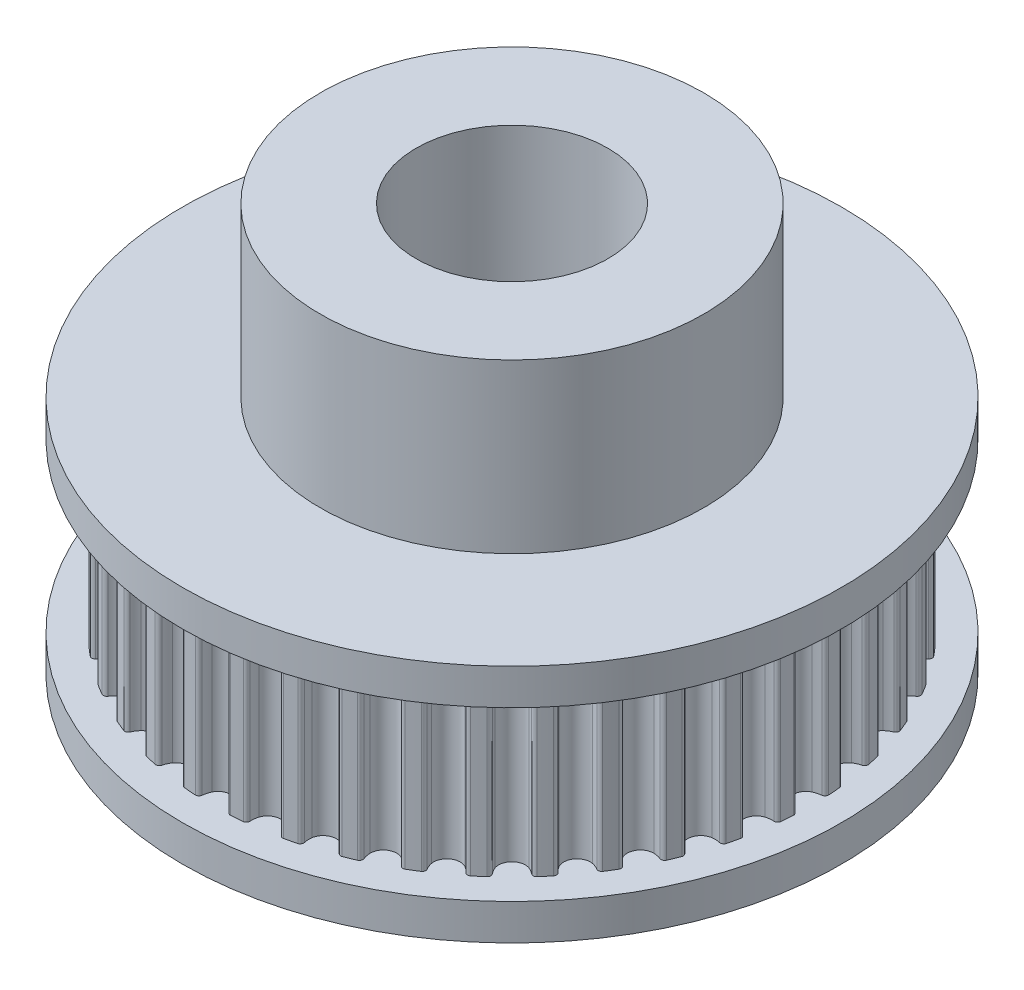
SolidWorks part; units mm, degrees
ref_plane "Front" through (0, 0, 0) normal (0, 0, 1) x (1, 0, 0)
ref_plane "Top" through (0, 0, 0) normal (0, 1, 0) x (1, 0, 0)
ref_plane "Right" through (0, 0, 0) normal (1, 0, 0) x (0, 0, -1)
sketch "Sketch1" plane through (0, 0, 0) normal (0, 0, 1) x (1, 0, 0)
  line L0 (0, 0) -> (0, 8.3172) construction
  line L1 (0, 0) -> (4, 0) construction
  line L2 (4, 0) -> (4, 17)
  line L3 (4, 0) -> (13.75, 0)
  line L4 (13.75, 0) -> (13.75, 1.5)
  line L5 (13.75, 1.5) -> (9.193, 1.5)
  line L6 (9.193, 1.5) -> (9.193, 8.5)
  line L7 (9.193, 8.5) -> (13.75, 8.5)
  line L8 (13.75, 8.5) -> (13.75, 10)
  line L9 (13.75, 10) -> (8, 10)
  line L10 (8, 10) -> (8, 17)
  line L11 (8, 17) -> (4, 17)
  dimension "D1" = 27.5
  dimension "D2" = 8
  dimension "D3" = 17
  dimension "D4" = 7
  dimension "D5" = 16
  dimension "D6" = 10
revolve "Revolve1" add sketch "Sketch1" angle 360 about L0
sketch "Sketch2" plane through (0, 1.5, 0) normal (0, 1, 0) x (1, 0, 0)
  circle A0 centre (0, 0) radius 4
  arc A1 (12.4796, -0.7303) -> (12.349, -0.5816) centre (12.3296, -0.7303) ccw
  arc A2 (12.0252, -0.4964) -> (12.349, -0.5816) centre (12.4379, 0.4144) ccw
  arc A3 (11.7184, 0) -> (12.0252, -0.4964) centre (12.2734, 0) ccw
  arc A4 (12.0252, 0.4964) -> (11.7184, 0) centre (12.2734, 0) ccw
  arc A5 (12.349, 0.5816) -> (12.0252, 0.4964) centre (12.4379, -0.4144) ccw
  arc A6 (12.349, 0.5816) -> (12.4796, 0.7303) centre (12.3296, 0.7303) ccw
  arc A7 (12.4796, 0.7303) -> (12.4402, 1.2309) centre (0.0225, 0.0018) ccw
  arc A8 (12.4402, 1.2309) -> (12.288, 1.3574) centre (12.2921, 1.2074) ccw
  arc A9 (11.9548, 1.3909) -> (12.288, 1.3574) centre (12.2199, 2.3551) ccw
  arc A10 (11.5741, 1.8332) -> (11.9548, 1.3909) centre (12.1223, 1.92) ccw
  arc A11 (11.7995, 2.3714) -> (11.5741, 1.8332) centre (12.1223, 1.92) ccw
  arc A12 (12.106, 2.5063) -> (11.7995, 2.3714) centre (12.3496, 1.5364) ccw
  arc A13 (12.106, 2.5063) -> (12.2117, 2.6736) centre (12.0636, 2.6501) ccw
  arc A14 (12.2117, 2.6736) -> (12.0945, 3.1618) centre (0.022, 0.0053) ccw
  arc A15 (12.0945, 3.1618) -> (11.9244, 3.2629) centre (11.9519, 3.1155) ccw
  arc A16 (11.59, 3.2439) -> (11.9244, 3.2629) centre (11.7011, 4.2377) ccw
  arc A17 (11.1448, 3.6212) -> (11.59, 3.2439) centre (11.6727, 3.7927) ccw
  arc A18 (11.2832, 4.1881) -> (11.1448, 3.6212) centre (11.6727, 3.7927) ccw
  arc A19 (11.5649, 4.3692) -> (11.2832, 4.1881) centre (11.9572, 3.4494) ccw
  arc A20 (11.5649, 4.3692) -> (11.6431, 4.551) centre (11.5005, 4.5047) ccw
  arc A21 (11.6431, 4.551) -> (11.451, 5.0149) centre (0.0209, 0.0087) ccw
  arc A22 (11.451, 5.0149) -> (11.2671, 5.0881) centre (11.3173, 4.9468) ccw
  arc A23 (10.9399, 5.017) -> (11.2671, 5.0881) centre (10.8941, 6.016) ccw
  arc A24 (10.4411, 5.32) -> (10.9399, 5.017) centre (10.9357, 5.572) ccw
  arc A25 (10.4891, 5.9016) -> (10.4411, 5.32) centre (10.9357, 5.572) ccw
  arc A26 (10.739, 6.1246) -> (10.4891, 5.9016) centre (11.2704, 5.2774) ccw
  arc A27 (10.739, 6.1246) -> (10.7879, 6.3164) centre (10.6542, 6.2483) ccw
  arc A28 (10.7879, 6.3164) -> (10.5255, 6.7445) centre (0.0193, 0.0118) ccw
  arc A29 (10.5255, 6.7445) -> (10.3324, 6.7881) centre (10.4042, 6.6563) ccw
  arc A30 (10.0203, 6.6666) -> (10.3324, 6.7881) centre (9.8189, 7.6461) ccw
  arc A31 (9.4804, 6.8879) -> (10.0203, 6.6666) centre (9.9294, 7.2141) ccw
  arc A32 (9.4368, 7.4698) -> (9.4804, 6.8879) centre (9.9294, 7.2141) ccw
  arc A33 (9.6487, 7.7291) -> (9.4368, 7.4698) centre (10.3061, 6.9755) ccw
  arc A34 (9.6487, 7.7291) -> (9.667, 7.9262) centre (9.5456, 7.838) ccw
  arc A35 (9.667, 7.9262) -> (9.3409, 8.308) centre (0.0172, 0.0147) ccw
  arc A36 (9.3409, 8.308) -> (9.1433, 8.3208) centre (9.2348, 8.2019) ccw
  arc A37 (8.8541, 8.1521) -> (9.1433, 8.3208) centre (8.5019, 9.088) ccw
  arc A38 (8.2861, 8.2861) -> (8.8541, 8.1521) centre (8.6786, 8.6786) ccw
  arc A39 (8.1521, 8.8541) -> (8.2861, 8.2861) centre (8.6786, 8.6786) ccw
  arc A40 (8.3208, 9.1433) -> (8.1521, 8.8541) centre (9.088, 8.5019) ccw
  arc A41 (8.3208, 9.1433) -> (8.308, 9.3409) centre (8.2019, 9.2348) ccw
  arc A42 (8.308, 9.3409) -> (7.9262, 9.667) centre (0.0147, 0.0172) ccw
  arc A43 (7.9262, 9.667) -> (7.7291, 9.6487) centre (7.838, 9.5456) ccw
  arc A44 (7.4698, 9.4368) -> (7.7291, 9.6487) centre (6.9755, 10.3061) ccw
  arc A45 (6.8879, 9.4804) -> (7.4698, 9.4368) centre (7.2141, 9.9294) ccw
  arc A46 (6.6666, 10.0203) -> (6.8879, 9.4804) centre (7.2141, 9.9294) ccw
  arc A47 (6.7881, 10.3324) -> (6.6666, 10.0203) centre (7.6461, 9.8189) ccw
  arc A48 (6.7881, 10.3324) -> (6.7445, 10.5255) centre (6.6563, 10.4042) ccw
  arc A49 (6.7445, 10.5255) -> (6.3164, 10.7879) centre (0.0118, 0.0193) ccw
  arc A50 (6.3164, 10.7879) -> (6.1246, 10.739) centre (6.2483, 10.6542) ccw
  arc A51 (5.9016, 10.4891) -> (6.1246, 10.739) centre (5.2774, 11.2704) ccw
  arc A52 (5.32, 10.4411) -> (5.9016, 10.4891) centre (5.572, 10.9357) ccw
  arc A53 (5.017, 10.9399) -> (5.32, 10.4411) centre (5.572, 10.9357) ccw
  arc A54 (5.0881, 11.2671) -> (5.017, 10.9399) centre (6.016, 10.8941) ccw
  arc A55 (5.0881, 11.2671) -> (5.0149, 11.451) centre (4.9468, 11.3173) ccw
  arc A56 (5.0149, 11.451) -> (4.551, 11.6431) centre (0.0087, 0.0209) ccw
  arc A57 (4.551, 11.6431) -> (4.3692, 11.5649) centre (4.5047, 11.5005) ccw
  arc A58 (4.1881, 11.2832) -> (4.3692, 11.5649) centre (3.4494, 11.9572) ccw
  arc A59 (3.6212, 11.1448) -> (4.1881, 11.2832) centre (3.7927, 11.6727) ccw
  arc A60 (3.2439, 11.59) -> (3.6212, 11.1448) centre (3.7927, 11.6727) ccw
  arc A61 (3.2629, 11.9244) -> (3.2439, 11.59) centre (4.2377, 11.7011) ccw
  arc A62 (3.2629, 11.9244) -> (3.1618, 12.0945) centre (3.1155, 11.9519) ccw
  arc A63 (3.1618, 12.0945) -> (2.6736, 12.2117) centre (0.0053, 0.022) ccw
  arc A64 (2.6736, 12.2117) -> (2.5063, 12.106) centre (2.6501, 12.0636) ccw
  arc A65 (2.3714, 11.7995) -> (2.5063, 12.106) centre (1.5364, 12.3496) ccw
  arc A66 (1.8332, 11.5741) -> (2.3714, 11.7995) centre (1.92, 12.1223) ccw
  arc A67 (1.3909, 11.9548) -> (1.8332, 11.5741) centre (1.92, 12.1223) ccw
  arc A68 (1.3574, 12.288) -> (1.3909, 11.9548) centre (2.3551, 12.2199) ccw
  arc A69 (1.3574, 12.288) -> (1.2309, 12.4402) centre (1.2074, 12.2921) ccw
  arc A70 (1.2309, 12.4402) -> (0.7303, 12.4796) centre (0.0018, 0.0225) ccw
  arc A71 (0.7303, 12.4796) -> (0.5816, 12.349) centre (0.7303, 12.3296) ccw
  arc A72 (0.4964, 12.0252) -> (0.5816, 12.349) centre (-0.4144, 12.4379) ccw
  arc A73 (0, 11.7184) -> (0.4964, 12.0252) centre (0, 12.2734) ccw
  arc A74 (-0.4964, 12.0252) -> (0, 11.7184) centre (0, 12.2734) ccw
  arc A75 (-0.5816, 12.349) -> (-0.4964, 12.0252) centre (0.4144, 12.4379) ccw
  arc A76 (-0.5816, 12.349) -> (-0.7303, 12.4796) centre (-0.7303, 12.3296) ccw
  arc A77 (-0.7303, 12.4796) -> (-1.2309, 12.4402) centre (-0.0018, 0.0225) ccw
  arc A78 (-1.2309, 12.4402) -> (-1.3574, 12.288) centre (-1.2074, 12.2921) ccw
  arc A79 (-1.3909, 11.9548) -> (-1.3574, 12.288) centre (-2.3551, 12.2199) ccw
  arc A80 (-1.8332, 11.5741) -> (-1.3909, 11.9548) centre (-1.92, 12.1223) ccw
  arc A81 (-2.3714, 11.7995) -> (-1.8332, 11.5741) centre (-1.92, 12.1223) ccw
  arc A82 (-2.5063, 12.106) -> (-2.3714, 11.7995) centre (-1.5364, 12.3496) ccw
  arc A83 (-2.5063, 12.106) -> (-2.6736, 12.2117) centre (-2.6501, 12.0636) ccw
  arc A84 (-2.6736, 12.2117) -> (-3.1618, 12.0945) centre (-0.0053, 0.022) ccw
  arc A85 (-3.1618, 12.0945) -> (-3.2629, 11.9244) centre (-3.1155, 11.9519) ccw
  arc A86 (-3.2439, 11.59) -> (-3.2629, 11.9244) centre (-4.2377, 11.7011) ccw
  arc A87 (-3.6212, 11.1448) -> (-3.2439, 11.59) centre (-3.7927, 11.6727) ccw
  arc A88 (-4.1881, 11.2832) -> (-3.6212, 11.1448) centre (-3.7927, 11.6727) ccw
  arc A89 (-4.3692, 11.5649) -> (-4.1881, 11.2832) centre (-3.4494, 11.9572) ccw
  arc A90 (-4.3692, 11.5649) -> (-4.551, 11.6431) centre (-4.5047, 11.5005) ccw
  arc A91 (-4.551, 11.6431) -> (-5.0149, 11.451) centre (-0.0087, 0.0209) ccw
  arc A92 (-5.0149, 11.451) -> (-5.0881, 11.2671) centre (-4.9468, 11.3173) ccw
  arc A93 (-5.017, 10.9399) -> (-5.0881, 11.2671) centre (-6.016, 10.8941) ccw
  arc A94 (-5.32, 10.4411) -> (-5.017, 10.9399) centre (-5.572, 10.9357) ccw
  arc A95 (-5.9016, 10.4891) -> (-5.32, 10.4411) centre (-5.572, 10.9357) ccw
  arc A96 (-6.1246, 10.739) -> (-5.9016, 10.4891) centre (-5.2774, 11.2704) ccw
  arc A97 (-6.1246, 10.739) -> (-6.3164, 10.7879) centre (-6.2483, 10.6542) ccw
  arc A98 (-6.3164, 10.7879) -> (-6.7445, 10.5255) centre (-0.0118, 0.0193) ccw
  arc A99 (-6.7445, 10.5255) -> (-6.7881, 10.3324) centre (-6.6563, 10.4042) ccw
  arc A100 (-6.6666, 10.0203) -> (-6.7881, 10.3324) centre (-7.6461, 9.8189) ccw
  arc A101 (-6.8879, 9.4804) -> (-6.6666, 10.0203) centre (-7.2141, 9.9294) ccw
  arc A102 (-7.4698, 9.4368) -> (-6.8879, 9.4804) centre (-7.2141, 9.9294) ccw
  arc A103 (-7.7291, 9.6487) -> (-7.4698, 9.4368) centre (-6.9755, 10.3061) ccw
  arc A104 (-7.7291, 9.6487) -> (-7.9262, 9.667) centre (-7.838, 9.5456) ccw
  arc A105 (-7.9262, 9.667) -> (-8.308, 9.3409) centre (-0.0147, 0.0172) ccw
  arc A106 (-8.308, 9.3409) -> (-8.3208, 9.1433) centre (-8.2019, 9.2348) ccw
  arc A107 (-8.1521, 8.8541) -> (-8.3208, 9.1433) centre (-9.088, 8.5019) ccw
  arc A108 (-8.2861, 8.2861) -> (-8.1521, 8.8541) centre (-8.6786, 8.6786) ccw
  arc A109 (-8.8541, 8.1521) -> (-8.2861, 8.2861) centre (-8.6786, 8.6786) ccw
  arc A110 (-9.1433, 8.3208) -> (-8.8541, 8.1521) centre (-8.5019, 9.088) ccw
  arc A111 (-9.1433, 8.3208) -> (-9.3409, 8.308) centre (-9.2348, 8.2019) ccw
  arc A112 (-9.3409, 8.308) -> (-9.667, 7.9262) centre (-0.0172, 0.0147) ccw
  arc A113 (-9.667, 7.9262) -> (-9.6487, 7.7291) centre (-9.5456, 7.838) ccw
  arc A114 (-9.4368, 7.4698) -> (-9.6487, 7.7291) centre (-10.3061, 6.9755) ccw
  arc A115 (-9.4804, 6.8879) -> (-9.4368, 7.4698) centre (-9.9294, 7.2141) ccw
  arc A116 (-10.0203, 6.6666) -> (-9.4804, 6.8879) centre (-9.9294, 7.2141) ccw
  arc A117 (-10.3324, 6.7881) -> (-10.0203, 6.6666) centre (-9.8189, 7.6461) ccw
  arc A118 (-10.3324, 6.7881) -> (-10.5255, 6.7445) centre (-10.4042, 6.6563) ccw
  arc A119 (-10.5255, 6.7445) -> (-10.7879, 6.3164) centre (-0.0193, 0.0118) ccw
  arc A120 (-10.7879, 6.3164) -> (-10.739, 6.1246) centre (-10.6542, 6.2483) ccw
  arc A121 (-10.4891, 5.9016) -> (-10.739, 6.1246) centre (-11.2704, 5.2774) ccw
  arc A122 (-10.4411, 5.32) -> (-10.4891, 5.9016) centre (-10.9357, 5.572) ccw
  arc A123 (-10.9399, 5.017) -> (-10.4411, 5.32) centre (-10.9357, 5.572) ccw
  arc A124 (-11.2671, 5.0881) -> (-10.9399, 5.017) centre (-10.8941, 6.016) ccw
  arc A125 (-11.2671, 5.0881) -> (-11.451, 5.0149) centre (-11.3173, 4.9468) ccw
  arc A126 (-11.451, 5.0149) -> (-11.6431, 4.551) centre (-0.0209, 0.0087) ccw
  arc A127 (-11.6431, 4.551) -> (-11.5649, 4.3692) centre (-11.5005, 4.5047) ccw
  arc A128 (-11.2832, 4.1881) -> (-11.5649, 4.3692) centre (-11.9572, 3.4494) ccw
  arc A129 (-11.1448, 3.6212) -> (-11.2832, 4.1881) centre (-11.6727, 3.7927) ccw
  arc A130 (-11.59, 3.2439) -> (-11.1448, 3.6212) centre (-11.6727, 3.7927) ccw
  arc A131 (-11.9244, 3.2629) -> (-11.59, 3.2439) centre (-11.7011, 4.2377) ccw
  arc A132 (-11.9244, 3.2629) -> (-12.0945, 3.1618) centre (-11.9519, 3.1155) ccw
  arc A133 (-12.0945, 3.1618) -> (-12.2117, 2.6736) centre (-0.022, 0.0053) ccw
  arc A134 (-12.2117, 2.6736) -> (-12.106, 2.5063) centre (-12.0636, 2.6501) ccw
  arc A135 (-11.7995, 2.3714) -> (-12.106, 2.5063) centre (-12.3496, 1.5364) ccw
  arc A136 (-11.5741, 1.8332) -> (-11.7995, 2.3714) centre (-12.1223, 1.92) ccw
  arc A137 (-11.9548, 1.3909) -> (-11.5741, 1.8332) centre (-12.1223, 1.92) ccw
  arc A138 (-12.288, 1.3574) -> (-11.9548, 1.3909) centre (-12.2199, 2.3551) ccw
  arc A139 (-12.288, 1.3574) -> (-12.4402, 1.2309) centre (-12.2921, 1.2074) ccw
  arc A140 (-12.4402, 1.2309) -> (-12.4796, 0.7303) centre (-0.0225, 0.0018) ccw
  arc A141 (-12.4796, 0.7303) -> (-12.349, 0.5816) centre (-12.3296, 0.7303) ccw
  arc A142 (-12.0252, 0.4964) -> (-12.349, 0.5816) centre (-12.4379, -0.4144) ccw
  arc A143 (-11.7184, 0) -> (-12.0252, 0.4964) centre (-12.2734, 0) ccw
  arc A144 (-12.0252, -0.4964) -> (-11.7184, 0) centre (-12.2734, 0) ccw
  arc A145 (-12.349, -0.5816) -> (-12.0252, -0.4964) centre (-12.4379, 0.4144) ccw
  arc A146 (-12.349, -0.5816) -> (-12.4796, -0.7303) centre (-12.3296, -0.7303) ccw
  arc A147 (-12.4796, -0.7303) -> (-12.4402, -1.2309) centre (-0.0225, -0.0018) ccw
  arc A148 (-12.4402, -1.2309) -> (-12.288, -1.3574) centre (-12.2921, -1.2074) ccw
  arc A149 (-11.9548, -1.3909) -> (-12.288, -1.3574) centre (-12.2199, -2.3551) ccw
  arc A150 (-11.5741, -1.8332) -> (-11.9548, -1.3909) centre (-12.1223, -1.92) ccw
  arc A151 (-11.7995, -2.3714) -> (-11.5741, -1.8332) centre (-12.1223, -1.92) ccw
  arc A152 (-12.106, -2.5063) -> (-11.7995, -2.3714) centre (-12.3496, -1.5364) ccw
  arc A153 (-12.106, -2.5063) -> (-12.2117, -2.6736) centre (-12.0636, -2.6501) ccw
  arc A154 (-12.2117, -2.6736) -> (-12.0945, -3.1618) centre (-0.022, -0.0053) ccw
  arc A155 (-12.0945, -3.1618) -> (-11.9244, -3.2629) centre (-11.9519, -3.1155) ccw
  arc A156 (-11.59, -3.2439) -> (-11.9244, -3.2629) centre (-11.7011, -4.2377) ccw
  arc A157 (-11.1448, -3.6212) -> (-11.59, -3.2439) centre (-11.6727, -3.7927) ccw
  arc A158 (-11.2832, -4.1881) -> (-11.1448, -3.6212) centre (-11.6727, -3.7927) ccw
  arc A159 (-11.5649, -4.3692) -> (-11.2832, -4.1881) centre (-11.9572, -3.4494) ccw
  arc A160 (-11.5649, -4.3692) -> (-11.6431, -4.551) centre (-11.5005, -4.5047) ccw
  arc A161 (-11.6431, -4.551) -> (-11.451, -5.0149) centre (-0.0209, -0.0087) ccw
  arc A162 (-11.451, -5.0149) -> (-11.2671, -5.0881) centre (-11.3173, -4.9468) ccw
  arc A163 (-10.9399, -5.017) -> (-11.2671, -5.0881) centre (-10.8941, -6.016) ccw
  arc A164 (-10.4411, -5.32) -> (-10.9399, -5.017) centre (-10.9357, -5.572) ccw
  arc A165 (-10.4891, -5.9016) -> (-10.4411, -5.32) centre (-10.9357, -5.572) ccw
  arc A166 (-10.739, -6.1246) -> (-10.4891, -5.9016) centre (-11.2704, -5.2774) ccw
  arc A167 (-10.739, -6.1246) -> (-10.7879, -6.3164) centre (-10.6542, -6.2483) ccw
  arc A168 (-10.7879, -6.3164) -> (-10.5255, -6.7445) centre (-0.0193, -0.0118) ccw
  arc A169 (-10.5255, -6.7445) -> (-10.3324, -6.7881) centre (-10.4042, -6.6563) ccw
  arc A170 (-10.0203, -6.6666) -> (-10.3324, -6.7881) centre (-9.8189, -7.6461) ccw
  arc A171 (-9.4804, -6.8879) -> (-10.0203, -6.6666) centre (-9.9294, -7.2141) ccw
  arc A172 (-9.4368, -7.4698) -> (-9.4804, -6.8879) centre (-9.9294, -7.2141) ccw
  arc A173 (-9.6487, -7.7291) -> (-9.4368, -7.4698) centre (-10.3061, -6.9755) ccw
  arc A174 (-9.6487, -7.7291) -> (-9.667, -7.9262) centre (-9.5456, -7.838) ccw
  arc A175 (-9.667, -7.9262) -> (-9.3409, -8.308) centre (-0.0172, -0.0147) ccw
  arc A176 (-9.3409, -8.308) -> (-9.1433, -8.3208) centre (-9.2348, -8.2019) ccw
  arc A177 (-8.8541, -8.1521) -> (-9.1433, -8.3208) centre (-8.5019, -9.088) ccw
  arc A178 (-8.2861, -8.2861) -> (-8.8541, -8.1521) centre (-8.6786, -8.6786) ccw
  arc A179 (-8.1521, -8.8541) -> (-8.2861, -8.2861) centre (-8.6786, -8.6786) ccw
  arc A180 (-8.3208, -9.1433) -> (-8.1521, -8.8541) centre (-9.088, -8.5019) ccw
  arc A181 (-8.3208, -9.1433) -> (-8.308, -9.3409) centre (-8.2019, -9.2348) ccw
  arc A182 (-8.308, -9.3409) -> (-7.9262, -9.667) centre (-0.0147, -0.0172) ccw
  arc A183 (-7.9262, -9.667) -> (-7.7291, -9.6487) centre (-7.838, -9.5456) ccw
  arc A184 (-7.4698, -9.4368) -> (-7.7291, -9.6487) centre (-6.9755, -10.3061) ccw
  arc A185 (-6.8879, -9.4804) -> (-7.4698, -9.4368) centre (-7.2141, -9.9294) ccw
  arc A186 (-6.6666, -10.0203) -> (-6.8879, -9.4804) centre (-7.2141, -9.9294) ccw
  arc A187 (-6.7881, -10.3324) -> (-6.6666, -10.0203) centre (-7.6461, -9.8189) ccw
  arc A188 (-6.7881, -10.3324) -> (-6.7445, -10.5255) centre (-6.6563, -10.4042) ccw
  arc A189 (-6.7445, -10.5255) -> (-6.3164, -10.7879) centre (-0.0118, -0.0193) ccw
  arc A190 (-6.3164, -10.7879) -> (-6.1246, -10.739) centre (-6.2483, -10.6542) ccw
  arc A191 (-5.9016, -10.4891) -> (-6.1246, -10.739) centre (-5.2774, -11.2704) ccw
  arc A192 (-5.32, -10.4411) -> (-5.9016, -10.4891) centre (-5.572, -10.9357) ccw
  arc A193 (-5.017, -10.9399) -> (-5.32, -10.4411) centre (-5.572, -10.9357) ccw
  arc A194 (-5.0881, -11.2671) -> (-5.017, -10.9399) centre (-6.016, -10.8941) ccw
  arc A195 (-5.0881, -11.2671) -> (-5.0149, -11.451) centre (-4.9468, -11.3173) ccw
  arc A196 (-5.0149, -11.451) -> (-4.551, -11.6431) centre (-0.0087, -0.0209) ccw
  arc A197 (-4.551, -11.6431) -> (-4.3692, -11.5649) centre (-4.5047, -11.5005) ccw
  arc A198 (-4.1881, -11.2832) -> (-4.3692, -11.5649) centre (-3.4494, -11.9572) ccw
  arc A199 (-3.6212, -11.1448) -> (-4.1881, -11.2832) centre (-3.7927, -11.6727) ccw
  arc A200 (-3.2439, -11.59) -> (-3.6212, -11.1448) centre (-3.7927, -11.6727) ccw
  arc A201 (-3.2629, -11.9244) -> (-3.2439, -11.59) centre (-4.2377, -11.7011) ccw
  arc A202 (-3.2629, -11.9244) -> (-3.1618, -12.0945) centre (-3.1155, -11.9519) ccw
  arc A203 (-3.1618, -12.0945) -> (-2.6736, -12.2117) centre (-0.0053, -0.022) ccw
  arc A204 (-2.6736, -12.2117) -> (-2.5063, -12.106) centre (-2.6501, -12.0636) ccw
  arc A205 (-2.3714, -11.7995) -> (-2.5063, -12.106) centre (-1.5364, -12.3496) ccw
  arc A206 (-1.8332, -11.5741) -> (-2.3714, -11.7995) centre (-1.92, -12.1223) ccw
  arc A207 (-1.3909, -11.9548) -> (-1.8332, -11.5741) centre (-1.92, -12.1223) ccw
  arc A208 (-1.3574, -12.288) -> (-1.3909, -11.9548) centre (-2.3551, -12.2199) ccw
  arc A209 (-1.3574, -12.288) -> (-1.2309, -12.4402) centre (-1.2074, -12.2921) ccw
  arc A210 (-1.2309, -12.4402) -> (-0.7303, -12.4796) centre (-0.0018, -0.0225) ccw
  arc A211 (-0.7303, -12.4796) -> (-0.5816, -12.349) centre (-0.7303, -12.3296) ccw
  arc A212 (-0.4964, -12.0252) -> (-0.5816, -12.349) centre (0.4144, -12.4379) ccw
  arc A213 (0, -11.7184) -> (-0.4964, -12.0252) centre (0, -12.2734) ccw
  arc A214 (0.4964, -12.0252) -> (0, -11.7184) centre (0, -12.2734) ccw
  arc A215 (0.5816, -12.349) -> (0.4964, -12.0252) centre (-0.4144, -12.4379) ccw
  arc A216 (0.5816, -12.349) -> (0.7303, -12.4796) centre (0.7303, -12.3296) ccw
  arc A217 (0.7303, -12.4796) -> (1.2309, -12.4402) centre (0.0018, -0.0225) ccw
  arc A218 (1.2309, -12.4402) -> (1.3574, -12.288) centre (1.2074, -12.2921) ccw
  arc A219 (1.3909, -11.9548) -> (1.3574, -12.288) centre (2.3551, -12.2199) ccw
  arc A220 (1.8332, -11.5741) -> (1.3909, -11.9548) centre (1.92, -12.1223) ccw
  arc A221 (2.3714, -11.7995) -> (1.8332, -11.5741) centre (1.92, -12.1223) ccw
  arc A222 (2.5063, -12.106) -> (2.3714, -11.7995) centre (1.5364, -12.3496) ccw
  arc A223 (2.5063, -12.106) -> (2.6736, -12.2117) centre (2.6501, -12.0636) ccw
  arc A224 (2.6736, -12.2117) -> (3.1618, -12.0945) centre (0.0053, -0.022) ccw
  arc A225 (3.1618, -12.0945) -> (3.2629, -11.9244) centre (3.1155, -11.9519) ccw
  arc A226 (3.2439, -11.59) -> (3.2629, -11.9244) centre (4.2377, -11.7011) ccw
  arc A227 (3.6212, -11.1448) -> (3.2439, -11.59) centre (3.7927, -11.6727) ccw
  arc A228 (4.1881, -11.2832) -> (3.6212, -11.1448) centre (3.7927, -11.6727) ccw
  arc A229 (4.3692, -11.5649) -> (4.1881, -11.2832) centre (3.4494, -11.9572) ccw
  arc A230 (4.3692, -11.5649) -> (4.551, -11.6431) centre (4.5047, -11.5005) ccw
  arc A231 (4.551, -11.6431) -> (5.0149, -11.451) centre (0.0087, -0.0209) ccw
  arc A232 (5.0149, -11.451) -> (5.0881, -11.2671) centre (4.9468, -11.3173) ccw
  arc A233 (5.017, -10.9399) -> (5.0881, -11.2671) centre (6.016, -10.8941) ccw
  arc A234 (5.32, -10.4411) -> (5.017, -10.9399) centre (5.572, -10.9357) ccw
  arc A235 (5.9016, -10.4891) -> (5.32, -10.4411) centre (5.572, -10.9357) ccw
  arc A236 (6.1246, -10.739) -> (5.9016, -10.4891) centre (5.2774, -11.2704) ccw
  arc A237 (6.1246, -10.739) -> (6.3164, -10.7879) centre (6.2483, -10.6542) ccw
  arc A238 (6.3164, -10.7879) -> (6.7445, -10.5255) centre (0.0118, -0.0193) ccw
  arc A239 (6.7445, -10.5255) -> (6.7881, -10.3324) centre (6.6563, -10.4042) ccw
  arc A240 (6.6666, -10.0203) -> (6.7881, -10.3324) centre (7.6461, -9.8189) ccw
  arc A241 (6.8879, -9.4804) -> (6.6666, -10.0203) centre (7.2141, -9.9294) ccw
  arc A242 (7.4698, -9.4368) -> (6.8879, -9.4804) centre (7.2141, -9.9294) ccw
  arc A243 (7.7291, -9.6487) -> (7.4698, -9.4368) centre (6.9755, -10.3061) ccw
  arc A244 (7.7291, -9.6487) -> (7.9262, -9.667) centre (7.838, -9.5456) ccw
  arc A245 (7.9262, -9.667) -> (8.308, -9.3409) centre (0.0147, -0.0172) ccw
  arc A246 (8.308, -9.3409) -> (8.3208, -9.1433) centre (8.2019, -9.2348) ccw
  arc A247 (8.1521, -8.8541) -> (8.3208, -9.1433) centre (9.088, -8.5019) ccw
  arc A248 (8.2861, -8.2861) -> (8.1521, -8.8541) centre (8.6786, -8.6786) ccw
  arc A249 (8.8541, -8.1521) -> (8.2861, -8.2861) centre (8.6786, -8.6786) ccw
  arc A250 (9.1433, -8.3208) -> (8.8541, -8.1521) centre (8.5019, -9.088) ccw
  arc A251 (9.1433, -8.3208) -> (9.3409, -8.308) centre (9.2348, -8.2019) ccw
  arc A252 (9.3409, -8.308) -> (9.667, -7.9262) centre (0.0172, -0.0147) ccw
  arc A253 (9.667, -7.9262) -> (9.6487, -7.7291) centre (9.5456, -7.838) ccw
  arc A254 (9.4368, -7.4698) -> (9.6487, -7.7291) centre (10.3061, -6.9755) ccw
  arc A255 (9.4804, -6.8879) -> (9.4368, -7.4698) centre (9.9294, -7.2141) ccw
  arc A256 (10.0203, -6.6666) -> (9.4804, -6.8879) centre (9.9294, -7.2141) ccw
  arc A257 (10.3324, -6.7881) -> (10.0203, -6.6666) centre (9.8189, -7.6461) ccw
  arc A258 (10.3324, -6.7881) -> (10.5255, -6.7445) centre (10.4042, -6.6563) ccw
  arc A259 (10.5255, -6.7445) -> (10.7879, -6.3164) centre (0.0193, -0.0118) ccw
  arc A260 (10.7879, -6.3164) -> (10.739, -6.1246) centre (10.6542, -6.2483) ccw
  arc A261 (10.4891, -5.9016) -> (10.739, -6.1246) centre (11.2704, -5.2774) ccw
  arc A262 (10.4411, -5.32) -> (10.4891, -5.9016) centre (10.9357, -5.572) ccw
  arc A263 (10.9399, -5.017) -> (10.4411, -5.32) centre (10.9357, -5.572) ccw
  arc A264 (11.2671, -5.0881) -> (10.9399, -5.017) centre (10.8941, -6.016) ccw
  arc A265 (11.2671, -5.0881) -> (11.451, -5.0149) centre (11.3173, -4.9468) ccw
  arc A266 (11.451, -5.0149) -> (11.6431, -4.551) centre (0.0209, -0.0087) ccw
  arc A267 (11.6431, -4.551) -> (11.5649, -4.3692) centre (11.5005, -4.5047) ccw
  arc A268 (11.2832, -4.1881) -> (11.5649, -4.3692) centre (11.9572, -3.4494) ccw
  arc A269 (11.1448, -3.6212) -> (11.2832, -4.1881) centre (11.6727, -3.7927) ccw
  arc A270 (11.59, -3.2439) -> (11.1448, -3.6212) centre (11.6727, -3.7927) ccw
  arc A271 (11.9244, -3.2629) -> (11.59, -3.2439) centre (11.7011, -4.2377) ccw
  arc A272 (11.9244, -3.2629) -> (12.0945, -3.1618) centre (11.9519, -3.1155) ccw
  arc A273 (12.0945, -3.1618) -> (12.2117, -2.6736) centre (0.022, -0.0053) ccw
  arc A274 (12.2117, -2.6736) -> (12.106, -2.5063) centre (12.0636, -2.6501) ccw
  arc A275 (11.7995, -2.3714) -> (12.106, -2.5063) centre (12.3496, -1.5364) ccw
  arc A276 (11.5741, -1.8332) -> (11.7995, -2.3714) centre (12.1223, -1.92) ccw
  arc A277 (11.9548, -1.3909) -> (11.5741, -1.8332) centre (12.1223, -1.92) ccw
  arc A278 (12.288, -1.3574) -> (11.9548, -1.3909) centre (12.2199, -2.3551) ccw
  arc A279 (12.288, -1.3574) -> (12.4402, -1.2309) centre (12.2921, -1.2074) ccw
  arc A280 (12.4402, -1.2309) -> (12.4796, -0.7303) centre (0.0225, -0.0018) ccw
  dimension "D1" = 8
extrude "Boss-Extrude1" add sketch "Sketch2" along normal up to surface (7 mm away) up to face at (0, 8.5, -13.75)
